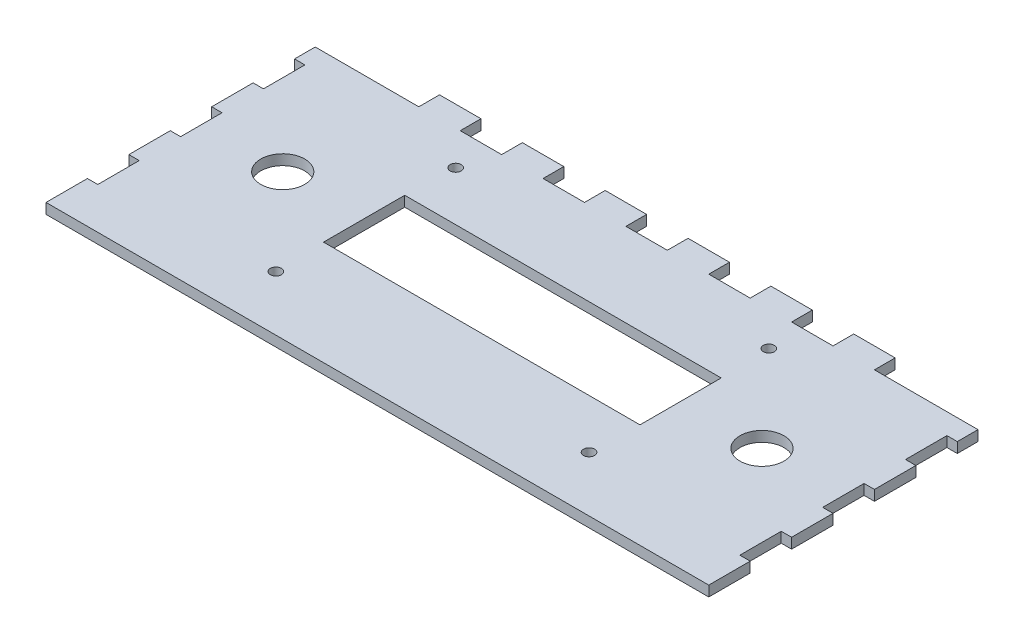
SolidWorks part; units mm, degrees
ref_plane "Front Plane" through (0, 0, 0) normal (0, 0, 1) x (1, 0, 0)
ref_plane "Top Plane" through (0, 0, 0) normal (0, 1, 0) x (1, 0, 0)
ref_plane "Right Plane" through (0, 0, 0) normal (1, 0, 0) x (0, 0, -1)
sketch "Sketch1" plane through (0, 0, 0) normal (0, 1, 0) x (1, 0, 0)
  line L1 (0, 0) -> (203.2, 0)
  line L2 (0, 0) -> (0, 88.9)
  line L3 (0, 88.9) -> (203.2, 88.9)
  line L4 (203.2, 0) -> (203.2, 88.9)
  dimension "D1" = 203.2
  dimension "D2" = 88.9
extrude "Boss-Extrude1" add sketch "Sketch1" along normal blind 3.175
sketch "Sketch2" plane through (0, 3.175, 0) normal (0, 1, 0) x (1, 0, 0)
  line L0 (203.2, 88.9) -> (0, 88.9) construction
  line L1 (19.05, 88.9) -> (31.75, 88.9)
  line L2 (19.05, 88.9) -> (19.05, 82.55)
  line L3 (19.05, 82.55) -> (31.75, 82.55)
  line L4 (31.75, 88.9) -> (31.75, 82.55)
  line L5 (0, 88.9) -> (0, 0) construction
  line L23 (203.2, 0) -> (203.2, 88.9) construction
  line L24 (0, 44.45) -> (203.2, 44.45) construction
  line L45 (0, 50.8) -> (0, 38.1)
  line L46 (0, 76.2) -> (3.175, 76.2)
  line L47 (0, 76.2) -> (0, 63.5)
  line L48 (0, 63.5) -> (3.175, 63.5)
  line L49 (3.175, 76.2) -> (3.175, 63.5)
  line L50 (0, 50.8) -> (3.175, 50.8)
  line L51 (3.175, 50.8) -> (3.175, 38.1)
  line L52 (0, 38.1) -> (3.175, 38.1)
  line L53 (0, 25.4) -> (0, 12.7)
  line L54 (0, 25.4) -> (3.175, 25.4)
  line L55 (3.175, 25.4) -> (3.175, 12.7)
  line L56 (0, 12.7) -> (3.175, 12.7)
  line L57 (44.45, 88.9) -> (44.45, 82.55)
  line L58 (44.45, 88.9) -> (57.15, 88.9)
  line L71 (57.15, 88.9) -> (57.15, 82.55)
  line L72 (44.45, 82.55) -> (57.15, 82.55)
  line L73 (69.85, 88.9) -> (69.85, 82.55)
  line L74 (69.85, 88.9) -> (82.55, 88.9)
  line L75 (82.55, 88.9) -> (82.55, 82.55)
  line L76 (69.85, 82.55) -> (82.55, 82.55)
  line L77 (95.25, 88.9) -> (95.25, 82.55)
  line L78 (95.25, 88.9) -> (107.95, 88.9)
  line L79 (107.95, 88.9) -> (107.95, 82.55)
  line L80 (95.25, 82.55) -> (107.95, 82.55)
  line L81 (120.65, 88.9) -> (120.65, 82.55)
  line L82 (120.65, 88.9) -> (133.35, 88.9)
  line L83 (133.35, 88.9) -> (133.35, 82.55)
  line L84 (120.65, 82.55) -> (133.35, 82.55)
  line L85 (146.05, 88.9) -> (146.05, 82.55)
  line L86 (146.05, 88.9) -> (158.75, 88.9)
  line L87 (158.75, 88.9) -> (158.75, 82.55)
  line L88 (146.05, 82.55) -> (158.75, 82.55)
  line L89 (171.45, 88.9) -> (171.45, 82.55)
  line L90 (171.45, 88.9) -> (184.15, 88.9)
  line L91 (184.15, 88.9) -> (184.15, 82.55)
  line L92 (171.45, 82.55) -> (184.15, 82.55)
  line L97 (196.85, 88.9) -> (196.85, 82.55) [skipped]
  line L98 (196.85, 88.9) -> (209.55, 88.9) [skipped]
  line L99 (209.55, 88.9) -> (209.55, 82.55) [skipped]
  line L100 (196.85, 82.55) -> (209.55, 82.55) [skipped]
  line L129 (101.6, 0) -> (101.6, 88.9) construction
  line L130 (0, 0) -> (203.2, 0) construction
  line L131 (203.2, 12.7) -> (200.025, 12.7)
  line L132 (200.025, 25.4) -> (200.025, 12.7)
  line L133 (203.2, 25.4) -> (200.025, 25.4)
  line L134 (203.2, 25.4) -> (203.2, 12.7)
  line L135 (203.2, 38.1) -> (200.025, 38.1)
  line L136 (200.025, 50.8) -> (200.025, 38.1)
  line L137 (203.2, 50.8) -> (200.025, 50.8)
  line L138 (200.025, 76.2) -> (200.025, 63.5)
  line L139 (203.2, 63.5) -> (200.025, 63.5)
  line L140 (203.2, 76.2) -> (203.2, 63.5)
  line L141 (203.2, 76.2) -> (200.025, 76.2)
  line L142 (203.2, 50.8) -> (203.2, 38.1)
  line L148 (0, 88.9) -> (19.05, 88.9)
  line L149 (0, 88.9) -> (0, 82.55)
  line L150 (0, 82.55) -> (19.05, 82.55)
  line L151 (19.05, 88.9) -> (19.05, 82.55)
  line L152 (184.15, 88.9) -> (203.2, 88.9)
  line L153 (184.15, 88.9) -> (184.15, 82.55)
  line L154 (184.15, 82.55) -> (203.2, 82.55)
  line L155 (203.2, 88.9) -> (203.2, 82.55)
  point P80 (101.6, 0)
  line M29 (0, 88.9) -> (0, 0)
  line M31 (203.2, 0) -> (203.2, 88.9)
  line M32 (203.2, 88.9) -> (0, 88.9)
  dimension "D1" = 19.05
  dimension "D2" = 12.7
  dimension "D3" = 6.35
  dimension "D5" = 12.7
  dimension "D6" = 12.7
  dimension "D7" = 12.7
  dimension "D8" = 3.175
  dimension "D10" = 12.7
  dimension "D9" = 3
  dimension "D4" = 8
extrude "Cut-Extrude1" cut sketch "Sketch2" against normal through all contours L150 L2 M29 M32 | L4 L2 L3 M32 | L57 L72 L71 M32 | L73 L76 L75 M32 | L77 L80 L79 M32 | L81 L84 L83 M32 | L85 L88 L87 M32 | L89 L92 L91 M32 | L91 L154 M31 M32 | L137 L136 L135 M31 | L133 L132 L131 M31 | L56 L55 L54 M29 | L52 L51 L50 M29 | L49 L46 L48 M29 | L138 L139 L140 L141 region at (201.6125, 3.175, -19.05) region at (201.6125, 3.175, -44.45) region at (177.8, 3.175, -85.725) region at (152.4, 3.175, -85.725) region at (127, 3.175, -85.725) region at (101.6, 3.175, -85.725) region at (76.2, 3.175, -85.725) region at (50.8, 3.175, -85.725) region at (1.5875, 3.175, -19.05) region at (1.5875, 3.175, -44.45) region at (1.5875, 3.175, -69.85) region at (25.4, 3.175, -85.725) region at (9.525, 3.175, -85.725) region at (190.5, 3.175, -85.725) region at (200.025, 3.175, -85.725)
sketch "Sketch3" plane through (0, 0, 0) normal (0, -1, 0) x (1, 0, 0)
  line L0 (3.175, -38.1) -> (3.175, -50.8) construction
  line L1 (53.086, -32.004) -> (150.114, -32.004)
  line L2 (53.086, -32.004) -> (53.086, -56.896)
  line L3 (53.086, -56.896) -> (150.114, -56.896)
  line L4 (150.114, -32.004) -> (150.114, -56.896)
  line L6 (0, 0) -> (203.2, 0) construction
  point P6 (3.175, -44.45)
  point P7 (53.086, -44.45)
  point P8 (101.6, -32.004)
  point P16 (101.6, 0)
  dimension "D1" = 97.028
  dimension "D2" = 24.892
extrude "Cut-Extrude2" cut sketch "Sketch3" against normal through all
hole_wizard "M3 Clearance Hole1" positions "Sketch7" profile "Sketch8" hole size "M3" standard "ANSI Metric" end condition through all
sketch "Sketch7" plane through (0, 0, 0) normal (0, -1, 0) x (-1, 0, 0)
  line L1 (-149.606, 72.009) -> (-53.594, 72.009) construction
  line L2 (-149.606, 72.009) -> (-149.606, 16.891) construction
  line L3 (-149.606, 16.891) -> (-53.594, 16.891) construction
  line L4 (-53.594, 72.009) -> (-53.594, 16.891) construction
  line L5 (-53.086, 56.896) -> (-150.114, 56.896) construction
  line L6 (-53.086, 32.004) -> (-53.086, 56.896) construction
  point P0 (-149.606, 72.009)
  point P2 (-149.606, 16.891)
  point P4 (-53.594, 16.891)
  point P6 (-53.594, 72.009)
  point P218 (-151.0496, 18.7902)
  point P219 (-149.0019, 19.8833)
  point P220 (-53.7685, 21.0814)
  point P221 (-53.7685, 67.0687)
  point P222 (-152.1452, 69.1699)
  point P225 (-101.6, 56.896)
  point P226 (-101.6, 72.009)
  point P229 (-53.086, 44.45)
  point P230 (-53.594, 44.45)
  dimension "D1" = 55.118
  dimension "D2" = 96.012
sketch "Sketch8" plane through (149.606, 0, -72.009) normal (1, 0, 0) x (0, 0, -1)
  line L0 (0, 0) -> (0, 3.175)
  line L1 (0, 3.175) -> (1.7, 3.175)
  line L2 (1.7, 3.175) -> (1.7, 0)
  line L5 (1.7, 0) -> (0, 0)
  line L11 (0, -6.35) -> (0, 107.95) construction
  dimension "Thru Hole Dia." = 3.4
  dimension "Thru Hole Depth" = 3.175
hole_wizard "M12 Clearance Hole1" positions "Sketch5" profile "Sketch6" hole size "M12" standard "ANSI Metric" end condition through all
sketch "Sketch5" plane through (0, 0, 0) normal (0, -1, 0) x (-1, 0, 0)
  line L0 (-150.114, 56.896) -> (-150.114, 32.004) construction
  line L1 (-150.114, 44.45) -> (-200.025, 44.45) construction
  line L2 (-200.025, 50.8) -> (-200.025, 38.1) construction
  line L4 (-53.086, 44.45) -> (-3.175, 44.45) construction
  line L5 (-53.086, 32.004) -> (-53.086, 56.896) construction
  line L6 (-3.175, 38.1) -> (-3.175, 50.8) construction
  point P0 (-175.0695, 44.45)
  point P2 (-28.1305, 44.45)
  point P7 (-150.114, 44.45)
  point P21 (0, 0)
  point P22 (-28.1305, 44.45)
  point P23 (-175.0695, 44.45)
sketch "Sketch6" plane through (175.0695, 0, -44.45) normal (1, 0, 0) x (0, 0, -1)
  line L0 (0, 0) -> (0, 3.175)
  line L1 (0, 3.175) -> (6.75, 3.175)
  line L2 (6.75, 3.175) -> (6.75, 0)
  line L5 (6.75, 0) -> (0, 0)
  line L11 (0, -6.35) -> (0, 107.95) construction
  dimension "Thru Hole Dia." = 13.5
  dimension "Thru Hole Depth" = 3.175
equation "\"screen board width\"= 98mm"
equation "\"screen board height\"= 60mm"
equation "\"lcd width\"= 97mm"
equation "\"lcd height\"= 25mm"
equation "\"lcd hole width\"= 96mm"
equation "\"lcd hole height\"= 55mm"
equation "\"D1@Sketch3\"=\"lcd width\""
equation "\"D2@Sketch3\"=\"lcd height\""
equation "\"D1@Sketch7\"=\"lcd hole height\""
equation "\"D2@Sketch7\"=\"lcd hole width\""
